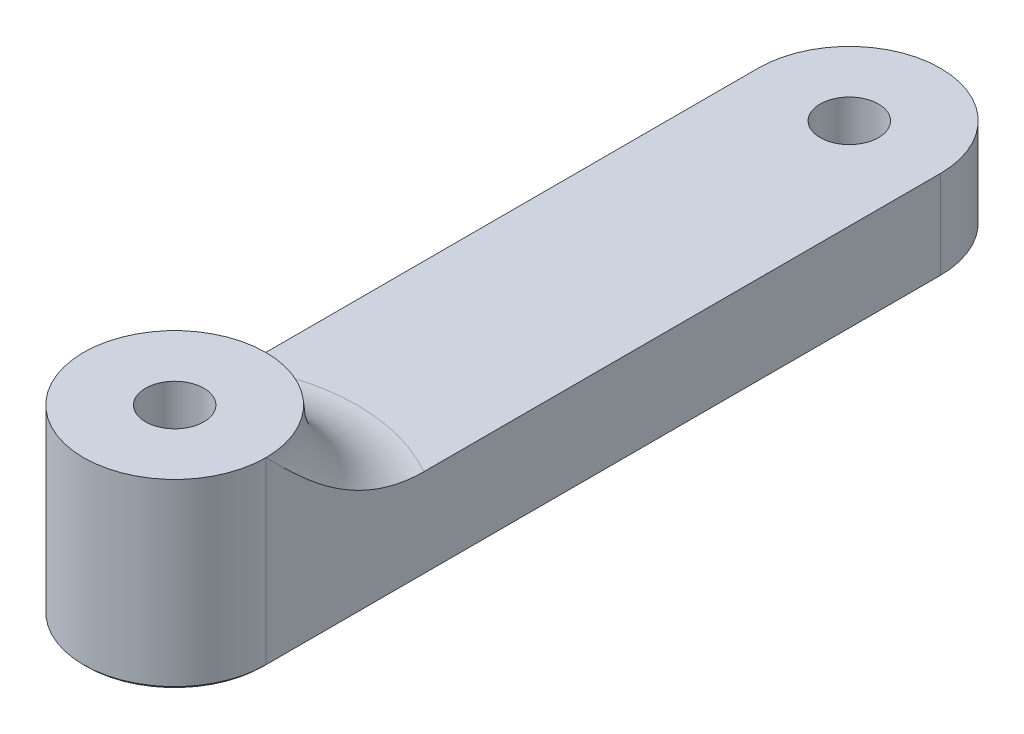
SolidWorks part; units mm, degrees
ref_plane "Front Plane" through (0, 0, 0) normal (0, 0, 1) x (1, 0, 0)
ref_plane "Top Plane" through (0, 0, 0) normal (0, 1, 0) x (1, 0, 0)
ref_plane "Right Plane" through (0, 0, 0) normal (1, 0, 0) x (0, 0, -1)
sketch "complete_sketch" plane through (0, 0, 0) normal (0, 1, 0) x (1, 0, 0)
  line L0 (0, 0) -> (0, 37) construction
  line L1 (-5, 0) -> (-5, 37)
  line L2 (5, 0) -> (5, 37)
  arc A0 (-5, 0) -> (5, 0) centre (0, 0) ccw
  arc A1 (5, 37) -> (-5, 37) centre (0, 37) ccw
  circle A2 centre (0, 37) radius 1.6
  circle A3 centre (0, 0) radius 1.6
  circle A4 centre (0, 0) radius 5
  point P3 (0, 18.5)
  dimension "D1" = 3.2
  dimension "D2" = 37
  dimension "D3" = 10
extrude "Body" add sketch "complete_sketch" along normal blind 5 contours A4 L2 A1 L1 A2 region at (0, 0, -22.1032)
extrude "rise_platform" add sketch "complete_sketch<3>" along normal blind 10 contours A3 A4 A0 region at (0, 0, -4.8586)
sketch "complete_sketch<3>" plane through (0, 0, 0) normal (0, 1, 0) x (1, 0, 0) same geometry as "complete_sketch"
chamfer "elephantsfoot_compensation" distance 0.16 angle 45 6 edges at (5, 0, -18.5) (0, 0, -42) (-5, 0, -18.5) (0, 0, -35.4) (0, 0, 1.6) (0, 0, 5)
fillet "Fillet1" radius 5 1 edges at (0, 5, -5)
